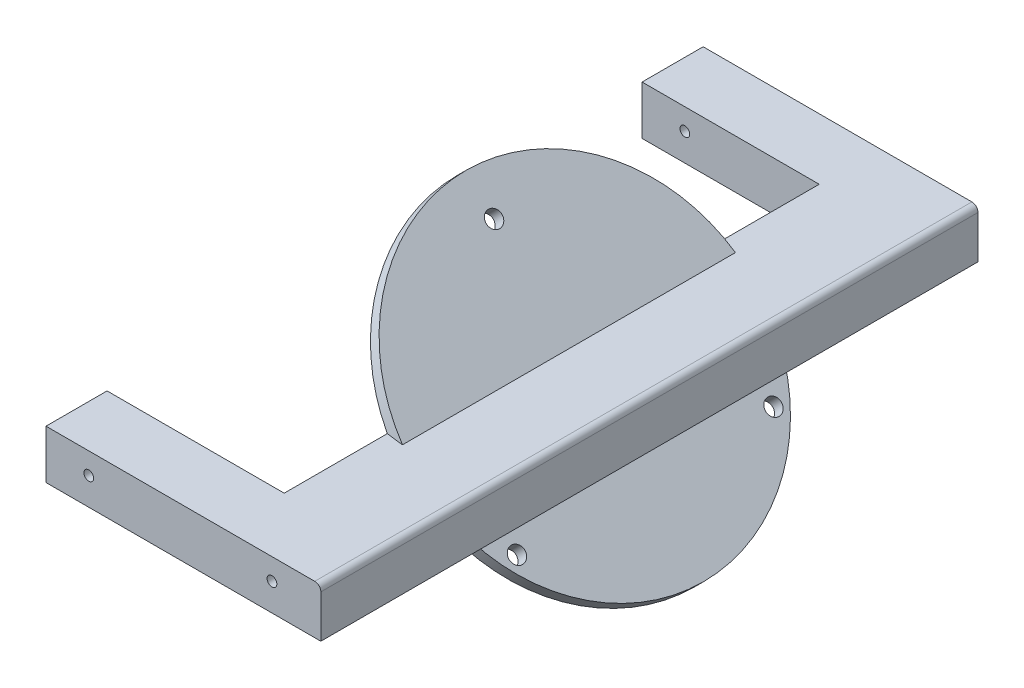
SolidWorks part; units mm, degrees
material "Nylon 101"
ref_plane "Front Plane" through (0, 0, 0) normal (0, 0, 1) x (1, 0, 0)
ref_plane "Top Plane" through (0, 0, 0) normal (0, 1, 0) x (1, 0, 0)
ref_plane "Right Plane" through (0, 0, 0) normal (1, 0, 0) x (0, 0, -1)
sketch "Sketch1" plane through (0, 0, 0) normal (0, 0, 1) x (1, 0, 0)
  line L4 (8, 4) -> (-8, 4)
  line L6 (0, -4) -> (-8, 4)
  line L7 (0, 4) -> (0, -4) construction
  line L8 (8, 4) -> (8, -4)
  line L9 (8, -4) -> (0, -4)
  dimension "D1" = 8
  dimension "D2" = 45
extrude "Base" add sketch "Sketch1" along normal mid plane 107.6
sketch "Sketch4" plane through (-2, -2, 0) normal (-0.7071, -0.7071, 0) x (0, 0, 1)
  line L0 (-53.8, 2.8284) -> (53.8, 2.8284) construction
  line L1 (-53.8, 8.4853) -> (-53.8, -2.8284) construction
  line L2 (53.8, 8.4853) -> (53.8, -2.8284) construction
  line L3 (0, 8.4853) -> (0, -2.8284) construction
  line L4 (53.8, 8.4853) -> (-53.8, 8.4853) construction
  line L6 (53.8, -2.8284) -> (-53.8, -2.8284) construction
  line L7 (-17.5, 20.3284) -> (17.5, 20.3284)
  line L8 (-17.5, 20.3284) -> (-17.5, -14.6716)
  line L9 (-17.5, -14.6716) -> (17.5, -14.6716)
  line L10 (17.5, 20.3284) -> (17.5, -14.6716)
  line L11 (-17.5, 20.3284) -> (17.5, -14.6716) construction
  line L12 (-17.5, -14.6716) -> (17.5, 20.3284) construction
  circle A0 centre (0, 2.8284) radius 27.5
  point P16 (0, 2.8284)
  point P17 (0, 2.8284)
  line M5 (53.8, 8.4853) -> (-53.8, 8.4853)
  dimension "D1" = 55
  dimension "D2" = 35
extrude "Boss-Extrude2" add sketch "Sketch4" against normal blind 2 contours A0 L8 L7 L10 M5 | L10 L7 L8 M5 | A0 L10 L9 L8 | A0 L8 M5 | L10 L8 L9 | L10 L8 M5 | A0 L10 M5 region at (-16.475, 12.475, 0) region at (-12.1872, 8.1872, 0) region at (0.1872, -4.1872, 0) region at (0.1872, -4.1872, -18.1422)
hole_wizard "M2 Clearance Hole2" positions "Sketch5" profile "Sketch6" hole size "M2" standard "ANSI Metric" end condition through all
sketch "Sketch5" plane through (-0.5858, -0.5858, 0) normal (0.7071, 0.7071, 0) x (0.7071, -0.7071, 0)
  line L4 (-8.4853, 0) -> (2.8284, 0) construction
  line L5 (-20.3284, 17.5) -> (-20.3284, -17.5) construction
  line L6 (-20.3284, -17.5) -> (14.6716, -17.5) construction
  line L7 (14.6716, 17.5) -> (14.6716, -17.5) construction
  line L8 (-20.3284, 17.5) -> (14.6716, 17.5) construction
  point P0 (-23.8284, 0)
  point P2 (11.1716, 21)
  point P4 (11.1716, -21)
  dimension "D1" = 3.5
  dimension "D2" = 3.5
  dimension "D3" = 3.5
  dimension "D4" = 3.5
sketch "Sketch6" plane through (-17.435, 16.2635, 0) normal (0, 0, 1) x (-0.7071, 0.7071, 0)
  line L0 (0, 0) -> (0, 29.5)
  line L1 (0, 29.5) -> (1.3, 29.5)
  line L2 (1.3, 29.5) -> (1.3, 0)
  line L5 (1.3, 0) -> (0, 0)
  line L11 (0, -6.35) -> (0, 107.95) construction
  dimension "Thru Hole Dia." = 2.6
  dimension "Thru Hole Depth" = 29.5
ref_plane "Plane1" through (-2, 2, 0) normal (0.7071, -0.7071, 0) x (0, 0, 1)
sketch "Sketch8" plane through (-2, 2, 0) normal (0.7071, -0.7071, 0) x (0, 0, 1)
  line L0 (0, 3.8284) -> (0, 2.8284)
  line L1 (27.5, 2.8284) -> (-27.5, 2.8284) construction
  line L2 (0, 2.8284) -> (-12, 2.8284)
  line L4 (0, 2.8284) -> (0, 10.3284) construction
  line L5 (-6.5, 10.3284) -> (-12, 2.8284)
  arc A1 (-6.5, 10.3284) -> (0, 3.8284) centre (0, 10.3284) ccw
  dimension "D2" = 6.5
  dimension "D1" = 1
  dimension "D3" = 12
revolve "Revolve1" add sketch "Sketch8" angle 360 about L4
fillet "Fillet1" radius 0.5 1 edges at (-13.8995, -0.7071, 0)
hole_wizard "Side Holes" positions "Sketch2" profile "Sketch3" hole size "M2x0.4" standard "ANSI Metric" end condition through all
sketch "Sketch2" plane through (0, 0, 53.8) normal (0, 0, 1) x (1, 0, 0)
  line L0 (0, 0.5) -> (0, 4) construction
  line L1 (8, 4) -> (-8, 4) construction
  line L3 (-4.5, 0.5) -> (8, 0.5) construction
  line L4 (-8, 4) -> (0, -4) construction
  line L6 (8, -4) -> (8, 4) construction
  point P0 (0, 0.5)
  dimension "D1" = 3.5
sketch "Sketch3" plane through (0, 0.5, 53.8) normal (1, 0, 0) x (0, -1, 0)
  line L0 (0, 0) -> (0, 107.6)
  line L1 (0, 107.6) -> (0.8, 107.6)
  line L2 (0.8, 107.6) -> (0.8, 0)
  line L5 (0.8, 0) -> (0, 0)
  line L11 (0, -6.35) -> (0, 107.95) construction
  dimension "Thru Hole Dia." = 1.6
  dimension "Thru Hole Depth" = 107.6
sketch "Sketch9" plane through (0, 0, 53.8) normal (0, 0, 1) x (1, 0, 0)
  line L0 (-8, 4) -> (0, -4)
  line L1 (0, -4) -> (-37, -4)
  line L2 (-37, -4) -> (-37, 4)
  line L3 (-37, 4) -> (-8, 4)
  line L4 (8, -4) -> (8, 4) construction
  dimension "D1" = 45
extrude "Side Arm" add sketch "Sketch9" against normal blind 10
mirror "Mirror1" about plane through (0, 0, 0) normal (0, 0, 1) of "Side Arm"
hole_wizard "Tap Drill for M2x0.4 Tap1" positions "Sketch10" profile "Sketch11" hole size "M2x0.4" standard "ANSI Metric" end condition through all
sketch "Sketch10" plane through (0, 0, 53.8) normal (0, 0, 1) x (1, 0, 0)
  line L0 (-37, 4) -> (-37, -4) construction
  point P0 (-30, 0.5)
  dimension "D1" = 7
sketch "Sketch11" plane through (-30, 0.5, 53.8) normal (1, 0, 0) x (0, -1, 0)
  line L0 (0, 0) -> (0, 107.6)
  line L1 (0, 107.6) -> (0.8, 107.6)
  line L2 (0.8, 107.6) -> (0.8, 0)
  line L5 (0.8, 0) -> (0, 0)
  line L11 (0, -6.35) -> (0, 107.95) construction
  dimension "Thru Hole Dia." = 1.6
  dimension "Thru Hole Depth" = 107.6
fillet "Fillet2" radius 1 1 edges at (8, 4, 0)
